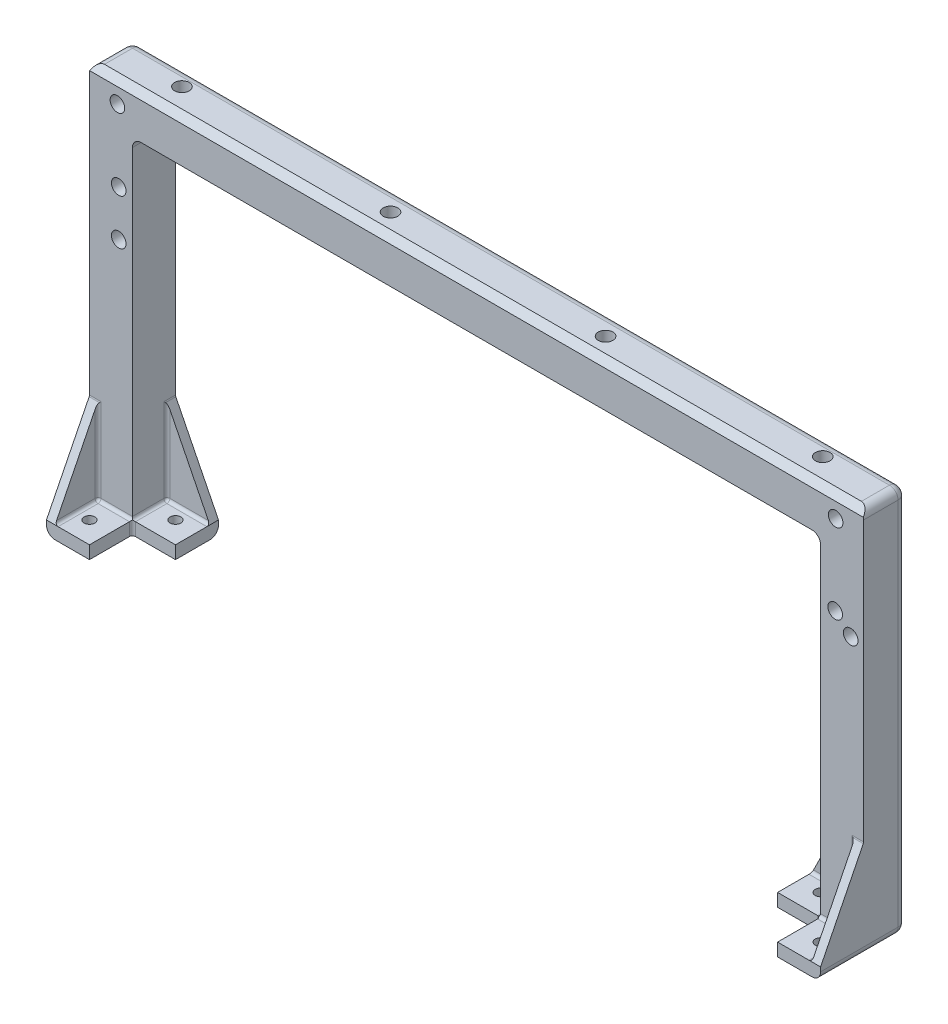
SolidWorks part; units mm, degrees
material "PLA"
ref_plane "Front Plane" through (0, 0, 0) normal (0, 0, 1) x (1, 0, 0)
ref_plane "Top Plane" through (0, 0, 0) normal (0, 1, 0) x (1, 0, 0)
ref_plane "Right Plane" through (0, 0, 0) normal (1, 0, 0) x (0, 0, -1)
sketch "Sketch1" plane through (0, 0, 0) normal (0, 0, 1) x (1, 0, 0)
  line L0 (0, 0) -> (39473.4142, 0) construction
  line L1 (0, 0) -> (0, 39473.4142) construction
  line L2 (-101.6, 0) -> (-101.6, 101.6)
  line L3 (-101.6, 101.6) -> (101.6, 101.6)
  line L4 (-101.6, 0) -> (-114.3, 0)
  line L5 (-114.3, 0) -> (-114.3, 114.3)
  line L6 (-114.3, 114.3) -> (114.3, 114.3)
  line L7 (114.3, 0) -> (114.3, 114.3)
  line L8 (101.6, 0) -> (114.3, 0)
  line L9 (101.6, 0) -> (101.6, 101.6)
  point P12 (0, 114.3)
  point P15 (0, 101.6)
  dimension "D1" = 101.6
  dimension "D3" = 114.3
  dimension "D2" = 203.2
  dimension "D4" = 228.6
extrude "Frame" add sketch "Sketch1" along normal blind 12.7
chamfer "Chamfer1" distance 1.905 angle 45 1 edges at (0, 114.3, 12.7)
sketch "Sketch8" plane through (0, 114.3, 0) normal (0, 1, 0) x (1, 0, 0)
  line L0 (-114.3, -10.795) -> (-114.3, 0) construction
  line L1 (114.3, 0) -> (-114.3, 0) construction
  line L2 (0, 0) -> (0, 50000) construction
  circle A0 centre (-94.615, -5.08) radius 2.159
  circle A1 centre (94.615, -5.08) radius 2.159
  dimension "D1" = 4.318
  dimension "D2" = 19.685
  dimension "D3" = 5.08
extrude "Top_Mounting_Holes" cut sketch "Sketch8" against normal blind 7.112
sketch "Sketch9" plane through (0, 0, 12.7) normal (0, 0, 1) x (1, 0, 0)
  line L0 (-114.3, 114.3) -> (114.3, 114.3) construction
  line L1 (-114.3, 112.395) -> (-114.3, 0) construction
  line L2 (0, 0) -> (0, 50000) construction
  circle A0 centre (-106.045, 107.95) radius 2.159
  circle A1 centre (106.045, 107.95) radius 2.159
  dimension "D3" = 4.318
  dimension "D1" = 6.35
  dimension "D2" = 8.255
extrude "Side_Mounting_Holes" cut sketch "Sketch9" against normal blind 7.112
sketch "Sketch14" plane through (0, 0, 0) normal (0, -1, 0) x (1, 0, 0)
  line L0 (-114.3, 0) -> (-114.3, 25.4)
  line L1 (-114.3, 12.7) -> (-114.3, 0) construction
  line L2 (-114.3, 25.4) -> (-101.6, 25.4)
  line L3 (-101.6, 25.4) -> (-101.6, 12.7)
  line L4 (-101.6, 12.7) -> (-88.9, 12.7)
  line L5 (-101.6, 12.7) -> (101.6, 12.7) construction
  line L6 (-88.9, 12.7) -> (-88.9, 0)
  line L7 (-101.6, 0) -> (101.6, 0) construction
  line L8 (-88.9, 0) -> (-114.3, 0)
  line L9 (-114.3, 12.7) -> (-101.6, 12.7) construction
  line L10 (-101.6, 12.7) -> (-101.6, 0) construction
  line L11 (0, 0) -> (0, 12.7) construction
  line L12 (-107.95, 25.4) -> (-107.95, 12.7) construction
  line L13 (-88.9, 6.35) -> (-101.6, 6.35) construction
  line L14 (-101.6, 12.7) -> (-101.6, 0) construction
  line L15 (88.9, 6.35) -> (101.6, 6.35) construction
  line L16 (107.95, 25.4) -> (107.95, 12.7) construction
  line L17 (88.9, 0) -> (114.3, 0)
  line L18 (88.9, 12.7) -> (88.9, 0)
  line L19 (101.6, 12.7) -> (88.9, 12.7)
  line L20 (101.6, 25.4) -> (101.6, 12.7)
  line L21 (114.3, 25.4) -> (101.6, 25.4)
  line L22 (114.3, 0) -> (114.3, 25.4)
  circle A0 centre (-107.95, 19.05) radius 1.5875
  circle A1 centre (-95.25, 6.35) radius 1.5875
  circle A2 centre (95.25, 6.35) radius 1.5875
  circle A3 centre (107.95, 19.05) radius 1.5875
  dimension "D4" = 3.175
  dimension "D5" = 19.05
  dimension "D1" = 12.7
  dimension "D2" = 12.7
  dimension "D3" = 19.05
extrude "Bottom_MountPlate" add sketch "Sketch14" against normal blind 3.81
sketch "Sketch15" plane through (-114.3, 0, 0) normal (-1, 0, 0) x (0, 0, 1)
  line L0 (25.4, 3.81) -> (12.7, 29.21)
  line L1 (12.7, 112.395) -> (12.7, 3.81) construction
  line L2 (12.7, 29.21) -> (12.7, 3.81)
  line L3 (12.7, 3.81) -> (25.4, 3.81)
  line L4 (25.4, 3.81) -> (12.7, 3.81) construction
  dimension "D1" = 25.4
extrude "Side_Gussets" add sketch "Sketch15" against normal blind 2.54
sketch "Sketch16" plane through (0, 0, 0) normal (0, 0, -1) x (-1, 0, 0)
  line L0 (88.9, 3.81) -> (101.6, 29.21)
  line L1 (101.6, 3.81) -> (101.6, 101.6) construction
  line L2 (101.6, 29.21) -> (101.6, 3.81)
  line L8 (88.9, 3.81) -> (101.6, 3.81)
  dimension "D1" = 25.4
extrude "Front_Gussets" add sketch "Sketch16" against normal blind 2.54
mirror "Mirror1" about plane through (0, 0, 0) normal (1, 0, 0) of "Side_Gussets"
mirror "Mirror2" about plane through (0, 0, 0) normal (1, 0, 0) of "Front_Gussets"
fillet "Fillet1" radius 0.889 10 edges at (111.76, 16.51, 12.7) (-111.76, 16.51, 12.7) (111.76, 3.81, 19.05) (106.68, 3.81, 12.7) (-106.68, 3.81, 12.7) (-111.76, 3.81, 19.05) (101.6, 29.21, 1.27) (113.03, 29.21, 12.7) (-101.6, 29.21, 1.27) (-113.03, 29.21, 12.7)
fillet "Fillet2" radius 0.889 8 edges at (101.6, 1.905, 12.7) (101.6, 16.6149, 2.54) (-101.6, 1.905, 12.7) (-101.6, 16.6149, 2.54) (-95.25, 3.81, 2.54) (-101.6, 3.81, 7.62) (101.6, 3.81, 7.62) (95.25, 3.81, 2.54)
sketch "Sketch10" plane through (0, 0, 12.7) normal (0, 0, 1) x (1, 0, 0)
  line L1 (114.3, 29.4199) -> (114.3, 112.395) construction
  line L2 (100.711, 0) -> (88.9, 0) construction
  line L3 (114.3, 0) -> (101.6, 0) construction
  circle A0 centre (105.918, 84.328) radius 2.159
  circle A1 centre (110.49, 80.01) radius 2.159
  point P10 (94.8055, 0)
  dimension "D1" = 4.318
  dimension "D2" = 4.318
  dimension "D4" = 3.81
  dimension "D6" = 8.382
  dimension "D5" = 84.328
  dimension "D3" = 80.01
extrude "RHS-Linkage-MountingHoles" cut sketch "Sketch10" against normal blind 7.112
sketch "Sketch11" plane through (0, 0, 12.7) normal (0, 0, 1) x (1, 0, 0)
  line L0 (-114.3, 112.395) -> (-114.3, 29.4199) construction
  line L2 (-101.6, 0) -> (-114.3, 0) construction
  circle A0 centre (-105.664, 73.4822) radius 2.159
  circle A1 centre (-105.664, 86.9442) radius 2.159
  dimension "D1" = 4.318
  dimension "D2" = 4.318
  dimension "D3" = 8.636
  dimension "D4" = 8.636
  dimension "D5" = 73.4822
  dimension "D6" = 86.9442
extrude "LHS-Linkage-MountingHoles" cut sketch "Sketch11" against normal blind 7.112
sketch "Sketch12" plane through (0, 101.6, 0) normal (0, -1, 0) x (1, 0, 0)
  line L0 (0, 0) -> (0, 12.7) construction
  line L1 (-101.6, 12.7) -> (101.6, 12.7) construction
  line L2 (0, 6.35) -> (-12.7, 6.35) construction
  circle A0 centre (-12.7, 6.35) radius 2.159
  circle A1 centre (12.7, 6.35) radius 2.159
  dimension "D1" = 4.318
  dimension "D2" = 25.4
extrude "FrontBrace_Mount_Holes" cut sketch "Sketch12" against normal blind 7.112
sketch "Sketch13" plane through (0, 114.3, 0) normal (0, 1, 0) x (1, 0, 0)
  line L0 (0, 0) -> (0, -12.7) construction
  line L1 (114.3, 0) -> (-114.3, 0) construction
  line L2 (114.3, -12.7) -> (-114.3, -12.7) construction
  line L3 (-31.75, -6.35) -> (0, -6.35) construction
  circle A0 centre (-31.75, -6.35) radius 2.159
  circle A1 centre (31.75, -6.35) radius 2.159
  dimension "D1" = 4.318
  dimension "D2" = 63.5
extrude "HC-SR04_Mount_Holes" cut sketch "Sketch13" against normal blind 7.112
fillet "Fillet3" radius 2.54 4 edges at (-114.3, 114.3, 5.3975) (114.3, 114.3, 5.3975) (114.3, 0, 12.7) (-114.3, 0, 12.7)
fillet "Fillet4" radius 2.54 11 edges at (-100.33, 0, 0) (-113.5561, 0.7439, 0) (-114.3, 57.15, 0) (-113.5561, 113.5561, 0) (0, 114.3, 0) (113.5561, 113.5561, 0) (114.3, 57.15, 0) (113.5561, 0.7439, 0) (100.33, 0, 0) (-101.6, 101.6, 6.35) (101.6, 101.6, 6.35)
equation "\"D1@Sketch1\"=\"D3@Sketch1\" - 0.5"
equation "\"D2@Sketch11\" = \"D1@Sketch11\""
equation "\"D2@Sketch10\"=\"D1@Sketch10\""
